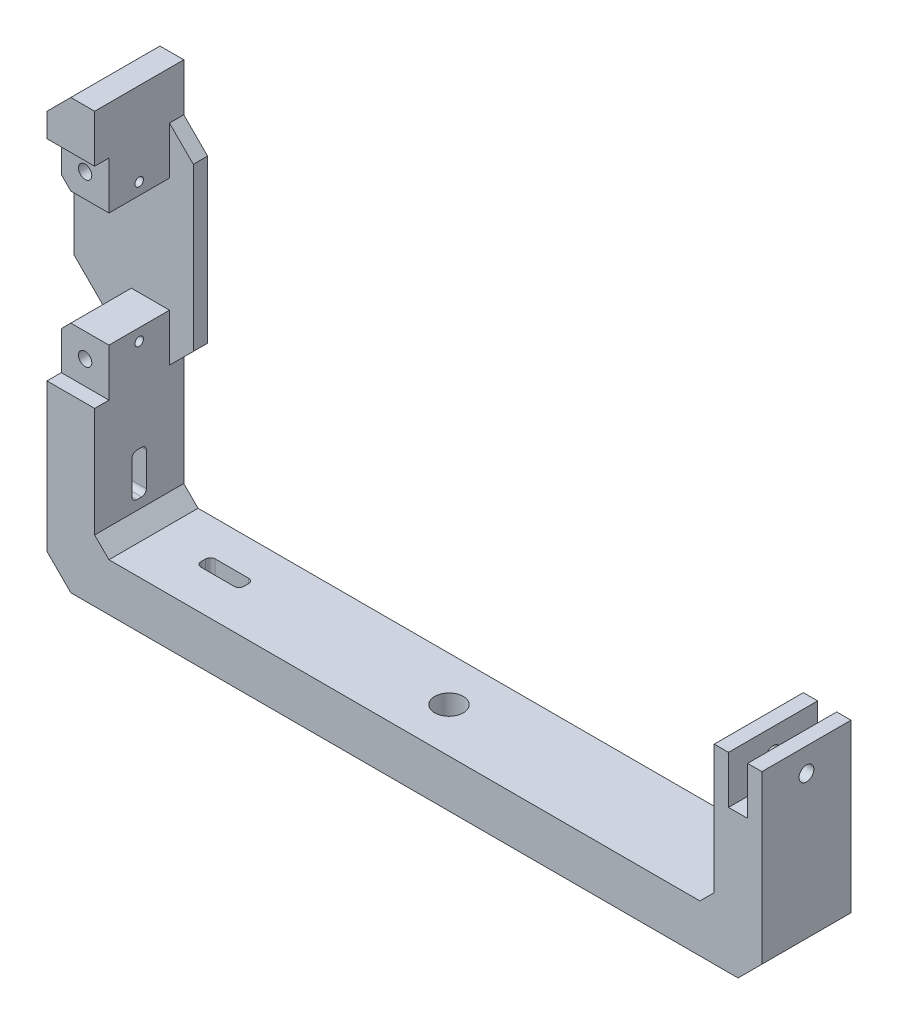
SolidWorks part; units mm, degrees
ref_plane "Front Plane" through (0, 0, 0) normal (0, 0, 1) x (1, 0, 0)
ref_plane "Top Plane" through (0, 0, 0) normal (0, 1, 0) x (1, 0, 0)
ref_plane "Right Plane" through (0, 0, 0) normal (1, 0, 0) x (0, 0, -1)
sketch "Sketch1" plane through (0, 0, 0) normal (0, 1, 0) x (1, 0, 0)
  line L1 (-75, 9.35) -> (75, 9.35)
  line L2 (-75, 9.35) -> (-75, -9.35)
  line L3 (-75, -9.35) -> (75, -9.35)
  line L4 (75, 9.35) -> (75, -9.35)
  line L5 (-75, 9.35) -> (75, -9.35) construction
  line L6 (-75, -9.35) -> (75, 9.35) construction
  point P0 (0, 0)
  dimension "D1" = 150
  dimension "D2" = 18.7
extrude "Boss-Extrude1" add sketch "Sketch1" along normal blind 10
sketch "Sketch2" plane through (0, 10, 0) normal (0, 1, 0) x (1, 0, 0)
  circle A0 centre (0, 0) radius 3
  dimension "D1" = 6
extrude "Cut-Extrude1" cut sketch "Sketch2" against normal blind 10
sketch "Sketch3" plane through (0, 0, 0) normal (0, -1, 0) x (1, 0, 0)
  circle A0 centre (7.25, 0) radius 0.9
  circle A1 centre (-7.25, 0) radius 0.9
  circle A2 centre (0, 0) radius 3 construction
  dimension "D1" = 1.8
  dimension "D2" = 1.8
  dimension "D3" = 7.25
  dimension "D4" = 7.25
extrude "Cut-Extrude2" cut sketch "Sketch3" against normal blind 5
sketch "Sketch4" plane through (0, 10, 0) normal (0, 1, 0) x (1, 0, 0)
  line L0 (-75, -9.35) -> (75, -9.35) construction
  line L1 (-75, 9.35) -> (-65, 9.35)
  line L2 (-75, 9.35) -> (-75, -9.35)
  line L3 (-75, -9.35) -> (-65, -9.35)
  line L4 (-65, 9.35) -> (-65, -9.35)
  line L6 (75, 9.35) -> (65, 9.35)
  line L7 (75, 9.35) -> (75, -9.35)
  line L8 (75, -9.35) -> (65, -9.35)
  line L9 (65, 9.35) -> (65, -9.35)
  dimension "D1" = 10
  dimension "D2" = 10
extrude "Boss-Extrude2" add sketch "Sketch4" along normal blind 80
sketch "Sketch5" plane through (0, 0, 9.35) normal (0, 0, 1) x (1, 0, 0)
  line L0 (-75, 90) -> (-75, 0) construction
  line L1 (-75, 70) -> (-65, 70)
  line L2 (-75, 70) -> (-75, 46)
  line L3 (-75, 46) -> (-65, 46)
  line L4 (-65, 70) -> (-65, 46)
  line L5 (-65, 90) -> (-65, 10) construction
  line L6 (-75, 90) -> (-65, 90) construction
  dimension "D1" = 24
  dimension "D2" = 20
extrude "Cut-Extrude3" cut sketch "Sketch5" against normal blind 15.7
sketch "Sketch6" plane through (0, 0, -6.35) normal (0, 0, 1) x (1, 0, 0)
  line L0 (-75, 46) -> (-65, 46) construction
  line L1 (-75, 70) -> (-85, 70)
  line L2 (-75, 70) -> (-75, 46)
  line L3 (-75, 46) -> (-85, 46)
  line L4 (-85, 70) -> (-85, 46)
  line L6 (-65, 70) -> (-60, 70)
  line L7 (-65, 70) -> (-65, 46)
  line L8 (-65, 46) -> (-60, 46)
  line L9 (-60, 70) -> (-60, 46)
  dimension "D1" = 0
  dimension "D2" = 10
  dimension "D3" = 5
extrude "Boss-Extrude3" add sketch "Sketch6" against normal blind 3
chamfer "Chamfer1" distance 10 angle 45 4 edges at (-65, 70, -7.85) (-65, 46, -7.85) (-75, 46, -7.85) (-75, 70, -7.85)
chamfer "Chamfer2" distance 2 angle 45 1 edges at (-75, 46, 1.5)
sketch "Sketch7" plane through (0, 0, 9.35) normal (0, 0, 1) x (1, 0, 0)
  line L0 (-65, 90) -> (-65, 70) construction
  line L1 (-75, 70) -> (-65, 70)
  line L2 (-75, 70) -> (-75, 80)
  line L3 (-75, 80) -> (-65, 80)
  line L4 (-65, 70) -> (-65, 80)
  line L6 (-65, 46) -> (-75, 46)
  line L7 (-65, 46) -> (-65, 36)
  line L8 (-65, 36) -> (-75, 36)
  line L9 (-75, 46) -> (-75, 36)
extrude "Cut-Extrude4" cut sketch "Sketch7" against normal blind 3
sketch "Sketch9" plane through (0, 0, 6.35) normal (0, 0, 1) x (1, 0, 0)
  line L0 (-75, 70) -> (-65, 70) construction
  line L1 (-65, 46) -> (-73, 46) construction
  circle A0 centre (-70, 75) radius 1.4
  circle A1 centre (-70, 41) radius 1.4
  dimension "D1" = 2.8
  dimension "D2" = 5
  dimension "D3" = 2.8
  dimension "D4" = 5
extrude "Cut-Extrude5" cut sketch "Sketch9" against normal blind 10
sketch "Sketch10" plane through (0, 0, 9.35) normal (0, 0, 1) x (1, 0, 0)
  line L0 (75, 90) -> (75, 0) construction
  line L1 (65, 90) -> (75, 90)
  line L2 (65, 90) -> (65, 40)
  line L3 (65, 40) -> (68, 40)
  line L4 (75, 90) -> (75, 40)
  line L5 (72, 40) -> (75, 40)
  line L7 (68, 40) -> (68, 30)
  line L8 (68, 30) -> (72, 30)
  line L9 (72, 40) -> (72, 30)
  point P7 (70, 40)
  dimension "D1" = 50
extrude "Cut-Extrude6" cut sketch "Sketch10" against normal blind 20
chamfer "Chamfer3" distance 5 angle 45 1 edges at (-75, 90, 0)
chamfer "Chamfer4" distance 5 angle 45 2 edges at (75, 0, 0) (-75, 0, 0)
chamfer "Chamfer5" distance 3 angle 45 2 edges at (65, 10, 0) (-65, 10, 0)
sketch "Sketch11" plane through (0, 10, 0) normal (0, 1, 0) x (1, 0, 0)
  line L0 (-62, 9.35) -> (-62, -9.35) construction
  line L1 (-52, 1.9503) -> (-43, 1.9503)
  line L2 (-52, 1.9503) -> (-52, -1.0497)
  line L3 (-52, -1.0497) -> (-43, -1.0497)
  line L4 (-43, 1.9503) -> (-43, -1.0497)
  line L5 (-52, 1.9503) -> (-43, -1.0497) construction
  line L6 (-52, -1.0497) -> (-43, 1.9503) construction
  point P0 (-47.5, 0.4503)
  dimension "D1" = 9
  dimension "D2" = 3
  dimension "D3" = 10
extrude "Cut-Extrude7" cut sketch "Sketch11" against normal blind 20
fillet "Fillet1" radius 1 4 edges at (-43, 5, -1.9503) (-43, 5, 1.0497) (-52, 5, 1.0497) (-52, 5, -1.9503)
sketch "Sketch12" plane through (-65, 0, 0) normal (1, 0, 0) x (0, 0, -1)
  line L0 (9.35, 36) -> (9.35, 13) construction
  line L1 (-1.5, 24) -> (1.5, 24)
  line L2 (-1.5, 24) -> (-1.5, 15)
  line L3 (-1.5, 15) -> (1.5, 15)
  line L4 (1.5, 24) -> (1.5, 15)
  line L5 (-1.5, 24) -> (1.5, 15) construction
  line L6 (-1.5, 15) -> (1.5, 24) construction
  line L8 (-9.35, 13) -> (9.35, 13) construction
  point P0 (0, 19.5)
  dimension "D1" = 9
  dimension "D2" = 3
  dimension "D3" = 7.85
  dimension "D4" = 2
extrude "Cut-Extrude8" cut sketch "Sketch12" against normal blind 20
fillet "Fillet2" radius 1 4 edges at (-70, 24, -1.5) (-70, 24, 1.5) (-70, 15, 1.5) (-70, 15, -1.5)
sketch "Sketch13" plane through (75, 0, 0) normal (1, 0, 0) x (0, 0, -1)
  line L0 (9.35, 40) -> (-9.35, 40) construction
  circle A0 centre (0, 35) radius 1.55
  dimension "D1" = 3.1
  dimension "D2" = 5
extrude "Cut-Extrude9" cut sketch "Sketch13" against normal blind 20
sketch "Sketch14" plane through (-65, 0, 0) normal (1, 0, 0) x (0, 0, -1)
  line L0 (6.35, 70) -> (-6.35, 70) construction
  line L1 (6.35, 46) -> (-6.35, 46) construction
  circle A0 centre (0, 72.5) radius 0.9
  circle A1 centre (0, 43.5) radius 0.9
  dimension "D1" = 1.8
  dimension "D2" = 1.8
  dimension "D3" = 2.5
  dimension "D4" = 2.5
extrude "Cut-Extrude10" cut sketch "Sketch14" against normal blind 3
chamfer "Chamfer6" distance 2 angle 45 1 edges at (-75, 70, 0)
